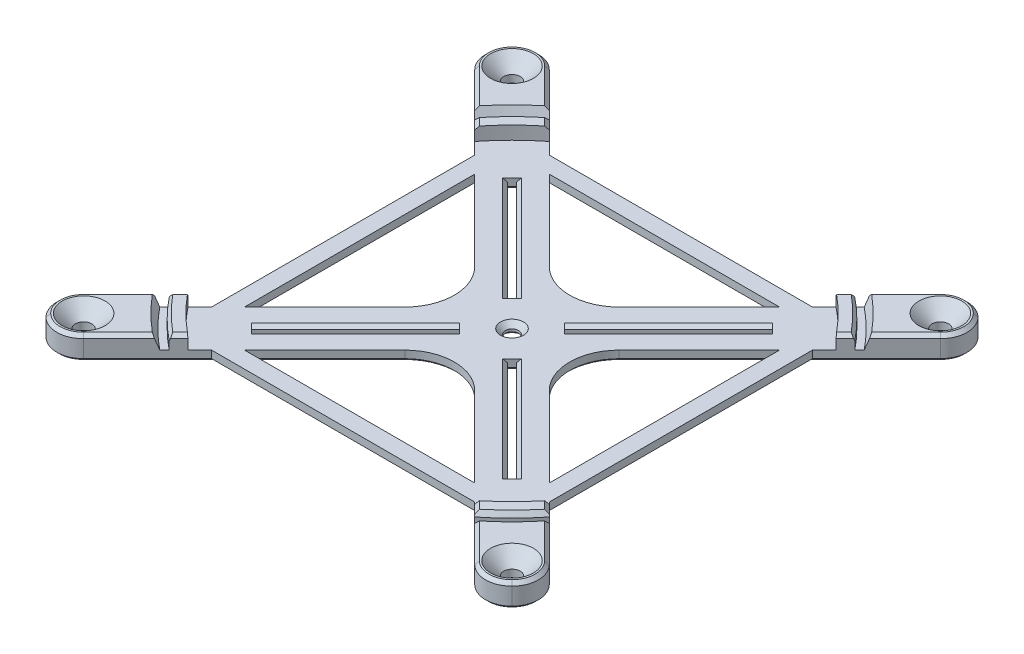
SolidWorks part; units mm, degrees
ref_plane "Спереди" through (0, 0, 0) normal (0, 0, 1) x (1, 0, 0)
ref_plane "Сверху" through (0, 0, 0) normal (0, 1, 0) x (1, 0, 0)
ref_plane "Справа" through (0, 0, 0) normal (1, 0, 0) x (0, 0, -1)
sketch "Эскиз1" plane through (0, 0, 0) normal (0, 1, 0) x (1, 0, 0)
  line L0 (-147.5, 147.5) -> (147.5, -147.5) construction
  line L1 (-147.5, -147.5) -> (147.5, -147.5) construction
  line L2 (-147.5, -147.5) -> (-147.5, 147.5) construction
  line L3 (-147.5, 147.5) -> (147.5, 147.5) construction
  line L4 (147.5, -147.5) -> (147.5, 147.5) construction
  line L5 (0, 147.5) -> (0, -147.5) construction
  line L6 (-147.5, 0) -> (147.5, 0) construction
  line L7 (130.1076, -152.7351) -> (-152.7351, 130.1076)
  line L8 (130.1076, -152.7351) -> (152.7351, -130.1076)
  line L9 (-152.7351, 130.1076) -> (-130.1076, 152.7351)
  line L10 (152.7351, -130.1076) -> (-130.1076, 152.7351)
  circle A0 centre (0, 0) radius 157.5 construction
  point P0 (0, 0)
  point P6 (0, 0)
  dimension "D5" = 32
  dimension "D1" = 295
  dimension "D2" = 295
  dimension "D3" = 400
  dimension "D4" = 45
extrude "Бобышка-Вытянуть1" add sketch "Эскиз1" along normal blind 14
sketch "Эскиз2" plane through (0, 0, 0) normal (0, 1, 0) x (1, 0, 0)
  line L0 (0, 0) -> (189.3234, 0) construction
  line L1 (0, 0) -> (209.4677, 209.4677) construction
  line L2 (-152.7351, -130.1076) -> (130.1076, 152.7351)
  line L3 (-152.7351, -130.1076) -> (-130.1076, -152.7351)
  line L4 (130.1076, 152.7351) -> (152.7351, 130.1076)
  line L5 (-130.1076, -152.7351) -> (152.7351, 130.1076)
  line L6 (-152.7351, -130.1076) -> (152.7351, 130.1076) construction
  line L7 (130.1076, 152.7351) -> (-130.1076, -152.7351) construction
  point P3 (141.4214, 141.4214)
  dimension "D1" = 32
  dimension "D2" = 400
  dimension "D3" = 45
extrude "Бобышка-Вытянуть2" add sketch "Эскиз2" along normal blind 14
fillet "Скругление1" radius 16 8 edges at (-130.1076, 7, -152.7351) (-152.7351, 7, -130.1076) (130.1076, 7, 152.7351) (152.7351, 7, 130.1076) (-130.1076, 7, 152.7351) (-152.7351, 7, 130.1076) (130.1076, 7, -152.7351) (152.7351, 7, -130.1076)
sketch "Эскиз3" plane through (0, 14, 0) normal (0, 1, 0) x (1, 0, 0)
  line L1 (-130, -130) -> (130, -130) construction
  line L2 (-130, -130) -> (-130, 130) construction
  line L3 (-130, 130) -> (130, 130) construction
  line L4 (130, -130) -> (130, 130) construction
  line L5 (0, 130) -> (0, -130) construction
  line L6 (-130, 0) -> (130, 0) construction
  circle A0 centre (-130, -130) radius 5
  circle A1 centre (-130, 130) radius 5
  circle A2 centre (130, 130) radius 5
  circle A3 centre (130, -130) radius 5
  circle A4 centre (0, 0) radius 4
  point P0 (0, 0)
  point P14 (0, 0)
  dimension "D1" = 10
  dimension "D3" = 8
  dimension "D2" = 260
  dimension "D4" = 367.6955
extrude "Вырез-Вытянуть1" cut sketch "Эскиз3" against normal through all
fillet "Скругление2" radius 30 4 edges at (22.6274, 7, 0) (0, 7, 22.6274) (-22.6274, 7, 0) (0, 7, -22.6274)
sketch "Эскиз4" plane through (0, 14, 0) normal (0, 1, 0) x (1, 0, 0)
  circle A0 centre (0, 0) radius 147
  dimension "D1" = 294
extrude "Вырез-Вытянуть-Тонкостенный1" [suppressed] cut sketch "Эскиз4" against normal blind 8 thin thin type one direction wall 11
chamfer "Фаска2" [suppressed] distance 1 angle 45
sketch "Эскиз5" plane through (0, 14, 0) normal (0, 1, 0) x (1, 0, 0)
  circle A0 centre (0, 0) radius 140
  dimension "D1" = 280
extrude "Вырез-Вытянуть2" cut sketch "Эскиз5" against normal blind 8
chamfer "Фаска3" distance 8 angle 45 4 edges at (-130, 14, -125) (130, 14, 135) (130, 14, -125) (-130, 14, 135)
chamfer "Фаска4" distance 2 angle 45 16 edges at (-102.9133, 14, -125.5407) (-130.1076, 14, -146.1076) (-125.5407, 14, -102.9133) (-146.1076, 14, -130.1076) (102.9133, 14, -125.5407) (125.5407, 14, -102.9133) (130.1076, 14, -146.1076) (146.1076, 14, -130.1076) (-125.5407, 14, 102.9133) (-146.1076, 14, 130.1076) (-102.9133, 14, 125.5407) (-130.1076, 14, 146.1076) (102.9133, 14, 125.5407) (130.1076, 14, 146.1076) (125.5407, 14, 102.9133) (146.1076, 14, 130.1076)
chamfer "Фаска5" distance 3 angle 45 1 edges at (0, 6, 4)
sketch "Эскиз8" plane through (0, 6, 0) normal (0, 1, 0) x (1, 0, 0)
  line L0 (0, 149.0517) -> (0, 0) construction
  line L1 (0, 0) -> (158.0685, 158.0685) construction
  line L2 (14.5163, 17.3447) -> (77.659, 80.4874)
  line L3 (14.5163, 17.3447) -> (17.3447, 14.5163)
  line L4 (77.659, 80.4874) -> (80.4874, 77.659)
  line L5 (17.3447, 14.5163) -> (80.4874, 77.659)
  line L6 (14.5163, 17.3447) -> (80.4874, 77.659) construction
  line L7 (77.659, 80.4874) -> (17.3447, 14.5163) construction
  line L8 (17.3447, -14.5163) -> (80.4874, -77.659)
  line L9 (17.3447, -14.5163) -> (14.5163, -17.3447)
  line L10 (14.5163, -17.3447) -> (77.659, -80.4874)
  line L11 (80.4874, -77.659) -> (77.659, -80.4874)
  line L12 (-14.5163, -17.3447) -> (-77.659, -80.4874)
  line L13 (-14.5163, -17.3447) -> (-17.3447, -14.5163)
  line L14 (-17.3447, -14.5163) -> (-80.4874, -77.659)
  line L15 (-77.659, -80.4874) -> (-80.4874, -77.659)
  line L16 (-17.3447, 14.5163) -> (-80.4874, 77.659)
  line L17 (-17.3447, 14.5163) -> (-14.5163, 17.3447)
  line L18 (-14.5163, 17.3447) -> (-77.659, 80.4874)
  line L19 (-80.4874, 77.659) -> (-77.659, 80.4874)
  point P5 (47.5019, 47.5019)
  point P24 (0, 0)
  dimension "D1" = 4
  dimension "D2" = 45
extrude "Вырез-Вытянуть4" cut sketch "Эскиз8" against normal through all
chamfer "Фаска6" distance 2 angle 45 8 edges at (-46.0877, 6, 48.9161) (-48.9161, 6, 46.0877) (48.9161, 6, -46.0877) (46.0877, 6, -48.9161) (46.0877, 6, 48.9161) (48.9161, 6, 46.0877) (-48.9161, 6, -46.0877) (-46.0877, 6, -48.9161)
sketch "Эскиз9" plane through (0, 6, 0) normal (0, 1, 0) x (1, 0, 0)
  line L0 (-86.1627, 102.497) -> (86.4506, 102.497)
  line L1 (-86.1627, 102.497) -> (-86.1627, 92.497)
  line L2 (86.4506, 102.497) -> (86.4506, 92.497)
  line L3 (-86.1627, 92.497) -> (86.4506, 92.497)
  line L4 (-86.1627, 102.497) -> (86.4506, 92.497) construction
  line L5 (86.4506, 102.497) -> (-86.1627, 92.497) construction
  line L6 (102.497, 86.1627) -> (102.497, -86.4506)
  line L7 (102.497, 86.1627) -> (92.497, 86.1627)
  line L8 (92.497, 86.1627) -> (92.497, -86.4506)
  line L9 (102.497, -86.4506) -> (92.497, -86.4506)
  line L10 (86.1627, -102.497) -> (-86.4506, -102.497)
  line L11 (86.1627, -102.497) -> (86.1627, -92.497)
  line L12 (86.1627, -92.497) -> (-86.4506, -92.497)
  line L13 (-86.4506, -102.497) -> (-86.4506, -92.497)
  line L14 (-102.497, -86.1627) -> (-102.497, 86.4506)
  line L15 (-102.497, -86.1627) -> (-92.497, -86.1627)
  line L16 (-92.497, -86.1627) -> (-92.497, 86.4506)
  line L17 (-102.497, 86.4506) -> (-92.497, 86.4506)
  point P1 (0.1439, 97.497)
  point P20 (0, 0)
  dimension "D1" = 10
extrude "Бобышка-Вытянуть3" add sketch "Эскиз9" against normal blind 6
chamfer "Фаска7" distance 1.5 angle 45 57 edges at (0, 0, 35.0538) (99.3317, 0, 121.9592) (45.5414, 0, 68.1688) (130.1076, 0, 146.1076) (146.1076, 0, 130.1076) (121.9592, 0, 99.3317) (68.1688, 0, 45.5414) (35.0538, 0, 0) (121.9592, 0, -99.3317) (68.1688, 0, -45.5414) (146.1076, 0, -130.1076) (130.1076, 0, -146.1076) (99.3317, 0, -121.9592) (45.5414, 0, -68.1688) (0, 0, -35.0538) (-99.3317, 0, -121.9592) (-45.5414, 0, -68.1688) (-130.1076, 0, -146.1076) (-146.1076, 0, -130.1076) (-68.1688, 0, -45.5414) (-121.9592, 0, -99.3317) (-35.0538, 0, 0) (-68.1688, 0, 45.5414) (-121.9592, 0, 99.3317) (-146.1076, 0, 130.1076) (-130.1076, 0, 146.1076) (-99.3317, 0, 121.9592) (-45.5414, 0, 68.1688) (79.0732, 0, -79.0732) (48.9161, 0, -46.0877) (15.9305, 0, -15.9305) (46.0877, 0, -48.9161) (79.0732, 0, 79.0732) (46.0877, 0, 48.9161) (15.9305, 0, 15.9305) (48.9161, 0, 46.0877) (-79.0732, 0, 79.0732) (-48.9161, 0, 46.0877) (-15.9305, 0, 15.9305) (-46.0877, 0, 48.9161) (-79.0732, 0, -79.0732) (-46.0877, 0, -48.9161) (-15.9305, 0, -15.9305) (-48.9161, 0, -46.0877) (-130, 0, 135) (0, 0, 4) (-130, 0, -125) (130, 0, -125) (130, 0, 135) (0, 0, -92.497) (92.497, 0, 0) (0, 0, 92.497) (0, 0, 102.497) (102.497, 0, 0) (0, 0, -102.497) (-102.497, 0, 0) (-92.497, 0, 0)
ref_plane "Плоскость1" through (0, 0, 0) normal (-0.7071, 0, 0.7071) x (0.7071, 0, 0.7071)
sketch "Эскиз10" plane through (-11.3137, 0, -11.3137) normal (-0.7071, 0, 0.7071) x (0.7071, 0, 0.7071)
  line L0 (164, 14) -> (164, 6)
  line L1 (164, 6) -> (168, 6)
  line L2 (168, 6) -> (171, 14)
  line L3 (171, 14) -> (164, 14)
  line L4 (16, 44.9308) -> (16, -21.492) construction
  line L5 (200, 0) -> (144.3313, 0) construction
  line L6 (155.2982, 14) -> (200, 14) construction
  point P9 (0, 0)
  dimension "D1" = 148
  dimension "D2" = 6
  dimension "D3" = 4
  dimension "D4" = 7
  dimension "D5" = 8
revolve "Вырез-Повернуть1" cut sketch "Эскиз10" angle 360 about L4
chamfer "Фаска8" distance 3 angle 30 4 edges at (-104.6518, 14, -104.6518) (-104.6518, 14, 104.6518) (104.6518, 14, 104.6518) (104.6518, 14, -104.6518) first distance on face at (-104.2677, 10.6666, -104.2677) first distance on face at (-104.2677, 10.6666, 104.2677) first distance on face at (104.2677, 10.6666, 104.2677) first distance on face at (104.2677, 10.6666, -104.2677)
